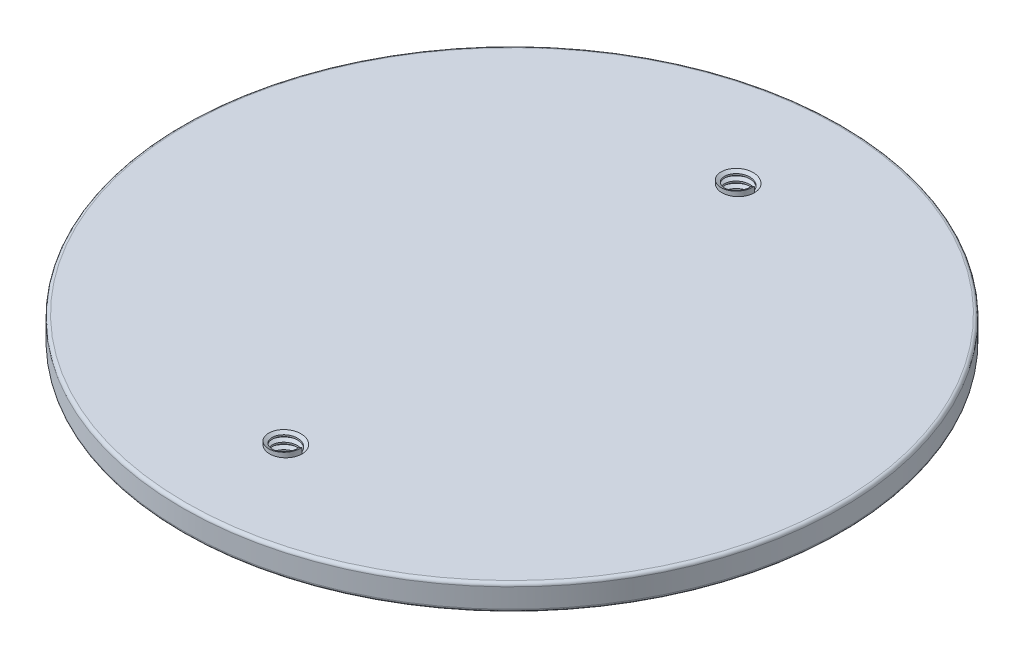
SolidWorks part; units mm, degrees
ref_plane "Front" through (0, 0, 0) normal (0, 0, 1) x (1, 0, 0)
ref_plane "Top" through (0, 0, 0) normal (0, 1, 0) x (1, 0, 0)
ref_plane "Right" through (0, 0, 0) normal (1, 0, 0) x (0, 0, -1)
sketch "Sketch2" plane through (0, 0, 0) normal (0, 1, 0) x (1, 0, 0)
  circle A0 centre (0, 0) radius 64.77
  dimension "D1" = 129.54
extrude "Boss-Extrude1" add sketch "Sketch2" along normal blind 5.08
sketch "Sketch3" plane through (0, 5.08, 0) normal (0, 1, 0) x (1, 0, 0)
  line L0 (0, 68.3509) -> (0, -70.9726) construction
  line L1 (-70.5981, 0) -> (70.5981, 0) construction
  circle A0 centre (0, 44.45) radius 3.175
  circle A1 centre (0, -44.45) radius 3.175
  dimension "D1" = 6.35
  dimension "D2" = 44.45
extrude "Cut-Extrude1" cut sketch "Sketch3" against normal through all
fillet "Fillet1" radius 0.635 2 edges at (0, 0, 64.77) (0, 5.08, 64.77)
thread "Thread1" pitch 1.27 method extrude profile "Thread Profile2" start angle 0, offset 0, length 0, pitch 1.27, diameter 6.35
ref_plane "Plane2" through (3.175, 0, 44.45) normal (0, 0, 1) x (1, 0, 0)
sketch "Thread Profile2" plane through (3.175, 0, 44.45) normal (0, 0, 1) x (1, 0, 0)
  line L0 (0, 0) -> (0, 1.27) construction
  line L11 (0, 0) -> (0, 1.1112)
  line L12 (0, 1.1112) -> (-0.6874, 0.7144)
  line L13 (-0.6874, 0.7144) -> (-0.6874, 0.3969)
  line L15 (-0.6874, 0.3969) -> (0, 0)
  line L17 (-0.6874, 0.5556) -> (0, 0.5556) construction
  point P2 (0, 0)
  dimension "Pitch" = 1.27
  dimension "Profile_Angle" = 60
  dimension "Profile_Land" = 0.3175
  dimension "Profile_Height" = 0.6874
thread "Thread2" pitch 1.27 method extrude profile "Thread Profile3" start angle 0, offset 0, length 0, pitch 1.27, diameter 6.35
ref_plane "Plane3" through (3.175, 0, -44.45) normal (0, 0, 1) x (1, 0, 0)
sketch "Thread Profile3" plane through (3.175, 0, -44.45) normal (0, 0, 1) x (1, 0, 0)
  line L0 (0, 0) -> (0, 1.27) construction
  line L11 (0, 0) -> (0, 1.1112)
  line L12 (0, 1.1112) -> (-0.6874, 0.7144)
  line L13 (-0.6874, 0.7144) -> (-0.6874, 0.3969)
  line L15 (-0.6874, 0.3969) -> (0, 0)
  line L17 (-0.6874, 0.5556) -> (0, 0.5556) construction
  point P2 (0, 0)
  dimension "Pitch" = 1.27
  dimension "Profile_Angle" = 60
  dimension "Profile_Land" = 0.3175
  dimension "Profile_Height" = 0.6874
